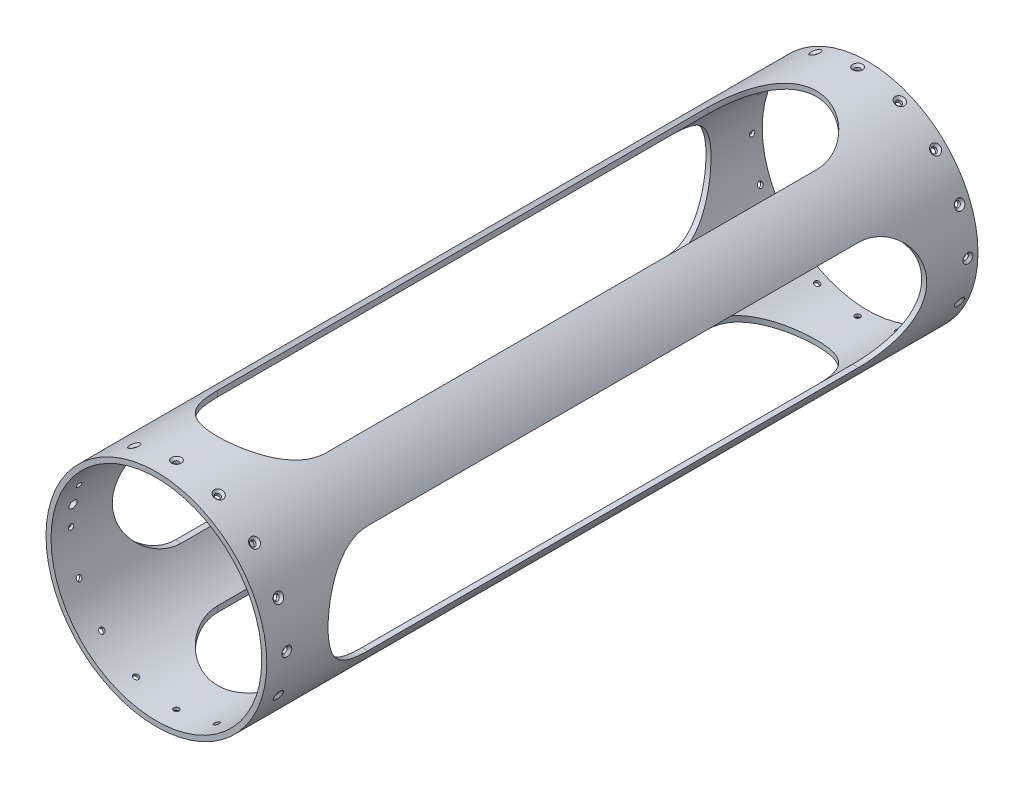
SolidWorks part; units mm, degrees
material "6061-T6 (SS)"
ref_plane "Front Plane" through (0, 0, 0) normal (0, 0, 1) x (1, 0, 0)
ref_plane "Top Plane" through (0, 0, 0) normal (0, 1, 0) x (1, 0, 0)
ref_plane "Right Plane" through (0, 0, 0) normal (1, 0, 0) x (0, 0, -1)
sketch "Sketch1" plane through (0, 0, 0) normal (0, 0, 1) x (1, 0, 0)
  circle A0 centre (0, 0) radius 66.675
  circle A1 centre (0, 0) radius 69.85
extrude "Extrude1" add sketch "Sketch1" along normal blind 228.2063
ref_plane "Plane2" through (0, 0, 215.5063) normal (0, 0, 1) x (1, 0, 0)
sketch "Sketch2" plane through (0, 0, 215.5063) normal (0, 0, 1) x (1, 0, 0)
  line L0 (0, 0) -> (-68.5079, 13.6271) construction
  line L1 (0, 0) -> (0, -69.85) construction
  circle A0 centre (0, 0) radius 69.85 construction
  point P0 (0, -69.85)
  dimension "D1" = 101.25
ref_plane "Plane3" through (0, -69.85, 215.5063) normal (0, -1, 0) x (1, 0, 0)
hole_wizard "CSK for M3 Flat Head Machine Screw1" positions "Sketch4" profile "Sketch3" countersink size "M3" standard "Ansi Metric" end condition through all
sketch "Sketch4" plane through (0, -69.85, 215.5063) normal (0, -1, 0) x (1, 0, 0)
  point P1 (0, 0)
sketch "Sketch3" plane through (0, -69.85, 215.5063) normal (1, 0, 0) x (0, 0, -1)
  line L0 (0, 0) -> (0, 161.1134)
  line L1 (0, 161.1134) -> (1.7, 161.1134)
  line L2 (1.7, 161.1134) -> (1.7, 1.45)
  line L3 (1.7, 1.45) -> (3.15, 0)
  line L5 (3.15, 0) -> (0, 0)
  line L6 (-1.7, 1.45) -> (-3.15, 0) construction
  line L11 (0, -6.35) -> (0, 107.95) construction
  dimension "Thru Hole Dia." = 3.4
  dimension "Thru Hole Depth" = 161.1134
  dimension "Near C'Sink Dia." = 6.3
  dimension "Near C'Sink Angle" = 90
sketch "Sketch5" plane through (0, 0, 0) normal (0, 1, 0) x (1, 0, 0)
  line L0 (0, 0) -> (34.29, 0)
  line L1 (69.85, 0) -> (-69.85, 0) construction
  line L2 (0, 0) -> (-34.29, 0)
  line L3 (66.675, 0) -> (-66.675, 0) construction
  line L4 (-34.29, 0) -> (-34.29, -155.1392)
  line L5 (34.29, 0) -> (34.29, -155.1392)
  line L6 (-34.29, -155.1392) -> (34.29, -155.1392) construction
  arc A0 (-34.29, -155.1392) -> (34.29, -155.1392) centre (0, -155.1392) ccw
  dimension "D1" = 155.1392
extrude "Extrude2" cut sketch "Sketch5" against normal through all and the other way through all
pattern_circular "CirPattern2" count 4 over 360 about axis through (0, 0, 228.2063) along (0, 0, -1) of "Extrude2"
pattern_circular "CirPattern1" count 16 over 360 about axis through (0, 0, 228.2063) along (0, 0, -1) of "CSK for M3 Flat Head Machine Screw1"
mirror "Mirror1" about plane through (0, 0, 0) normal (0, 0, 1) of "CirPattern2", "Extrude2", "Extrude1", "CirPattern1", "CSK for M3 Flat Head Machine Screw1"
sketch "Sketch6" plane through (0, 0, -228.2063) normal (0, 0, -1) x (-1, 0, 0)
  circle A0 centre (0, 0) radius 69.85
extrude "Extrude3" cut sketch "Sketch6" against normal blind 6.35
ref_plane "Plane4" through (-68.5079, 13.6271, 215.5063) normal (-0.9808, 0.1951, 0) x (-0.1951, -0.9808, 0)
hole_wizard "#10 Clearance Hole1" positions "Sketch10" profile "Sketch9" hole size "#10" standard "Ansi Inch"
sketch "Sketch10" plane through (-68.5079, 13.6271, 215.5063) normal (-0.9808, 0.1951, 0) x (-0.1951, -0.9808, 0)
  point P1 (0, 0)
sketch "Sketch9" plane through (-68.5079, 13.6271, 215.5063) normal (0, 0, 1) x (-0.1951, -0.9808, 0)
  line L0 (0, 0) -> (0, 11.1858)
  line L1 (0, 11.1858) -> (2.5527, 9.652)
  line L2 (2.5527, 9.652) -> (2.5527, 0)
  line L5 (2.5527, 0) -> (0, 0)
  line L10 (0, 11.1858) -> (-2.5527, 9.652) construction
  line L11 (0, -6.35) -> (0, 107.95) construction
  dimension "Hole Dia." = 5.1054
  dimension "Hole Depth" = 9.652
  dimension "Drill Angle" = 118
